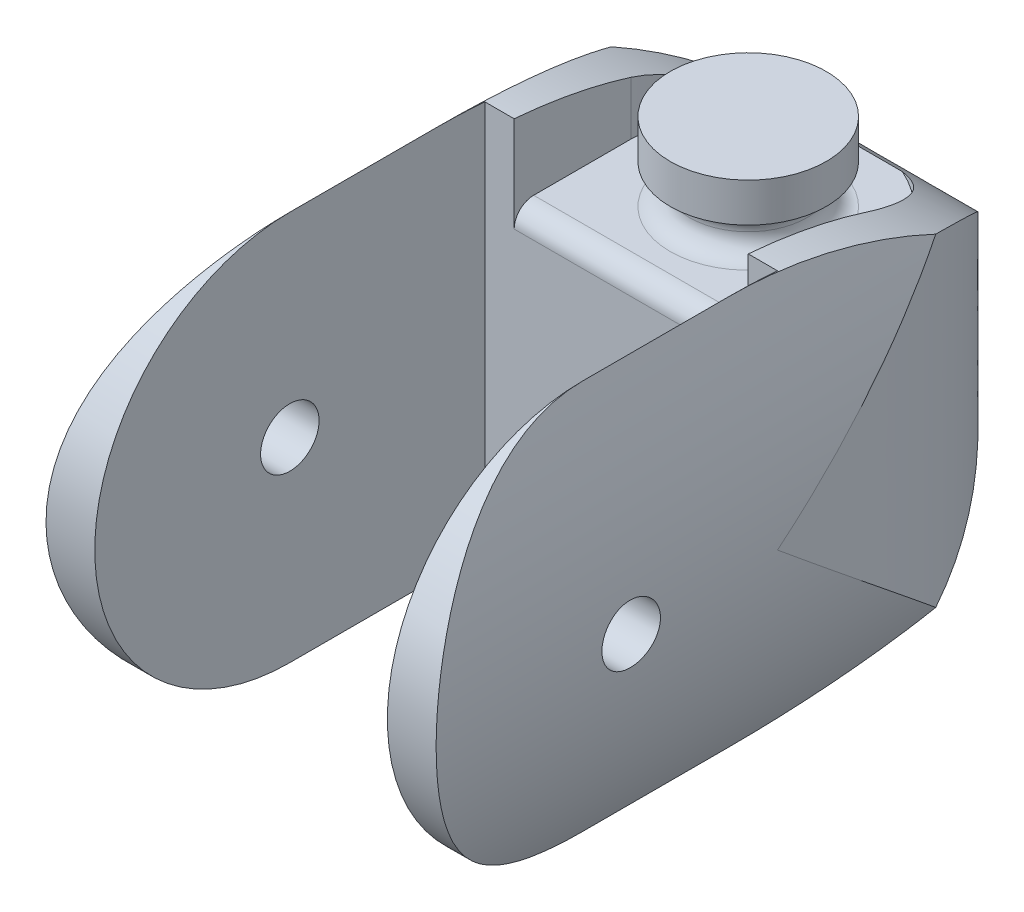
SolidWorks part; units mm, degrees
ref_plane "Alzado" through (0, 0, 0) normal (0, 0, 1) x (1, 0, 0)
ref_plane "Planta" through (0, 0, 0) normal (0, 1, 0) x (1, 0, 0)
ref_plane "Vista lateral" through (0, 0, 0) normal (1, 0, 0) x (0, 0, -1)
sketch "Croquis1" plane through (0, 0, 0) normal (0, 0, 1) x (1, 0, 0)
  line L1 (-7.5, 10) -> (7.5, 10)
  line L3 (-7.5, -10) -> (7.5, -10)
  line L5 (-7.5, 10) -> (7.5, -10) construction
  line L6 (-7.5, -10) -> (7.5, 10) construction
  arc A0 (-7.5, 10) -> (-7.5, -10) centre (11.25, 0) ccw
  arc A1 (7.5, -10) -> (7.5, 10) centre (-11.25, 0) ccw
  point P0 (0, 0)
  point P6 (-10, 0)
  point P7 (10, 0)
  dimension "D1" = 15
  dimension "D2" = 20
  dimension "D3" = 20
extrude "Saliente-Extruir1" add sketch "Croquis1" along normal blind 35
sketch "Croquis3" plane through (0, 0, 35) normal (0, 0, 1) x (1, 0, 0)
  line L0 (-7.5, -10) -> (7.5, -10) construction
  circle A0 centre (0, -7) radius 1.5
  dimension "D2" = 3
  dimension "D1" = 3
extrude "Cortar-Extruir2" cut sketch "Croquis3" against normal through all
sketch "Croquis6" plane through (0, 0, 35) normal (0, 0, 1) x (1, 0, 0)
  line L1 (-7.5, 10) -> (7.5, 10)
  line L2 (-7.5, 10) -> (-7.5, -10)
  line L3 (-7.5, -10) -> (7.5, -10)
  line L4 (7.5, 10) -> (7.5, -10)
  line L5 (-7.5, 10) -> (7.5, -10) construction
  line L6 (-7.5, -10) -> (7.5, 10) construction
  point P0 (0, 0)
extrude "Cortar-Extruir4" cut sketch "Croquis6" against normal blind 20
sketch "Croquis7" plane through (0, 0, 0) normal (1, 0, 0) x (0, 0, -1)
  line L0 (-35, 10) -> (-35, -10) construction
  line L2 (-25, -10) -> (-41, -10)
  line L4 (-25, 10) -> (-41, 10)
  line L5 (-41, -10) -> (-41, 10)
  arc A0 (-25, 10) -> (-25, -10) centre (-25, 0) ccw
  circle A1 centre (-25, 0) radius 1.5
  dimension "D2" = 3
  dimension "D1" = 10
  dimension "D3" = 16
extrude "Cortar-Extruir5" cut sketch "Croquis7" against normal through all both and the other way through all
sketch "Croquis2" plane through (0, 0, 0) normal (0, 1, 0) x (1, 0, 0)
  line L0 (10, -23.5) -> (10, 0) construction
  line L1 (7.5, 0) -> (-7.5, 0) construction
  line L9 (-1.2618, 0) -> (1.2618, 0)
  line L12 (-10, -17.5) -> (-10, 3.2701)
  line L13 (-10, 3.2701) -> (10, 3.2701)
  line L14 (10, -17.5) -> (10, 3.2701)
  ellipse E0 centre (0, -17.5) end of major axis (0, 0.141) minor radius 10 (-1.2618, 0) -> (-10, -17.5) ccw
  ellipse E1 centre (0, -17.5) end of major axis (0, 0.141) minor radius 10 (10, -17.5) -> (1.2618, 0) ccw
  dimension "D1" = 10
  dimension "D2" = 17.5
extrude "Cortar-Extruir1" cut sketch "Croquis2" against normal through all both and the other way through all
sketch "Croquis5" plane through (0, 0, 0) normal (1, 0, 0) x (0, 0, -1)
  line L0 (-15, -10) -> (-5.8316, -10) construction
  line L2 (-17.5, -10) -> (6.25, -10)
  line L4 (-17.5, 10) -> (6.25, 10)
  line L5 (6.25, -10) -> (6.25, 10)
  ellipse E0 centre (-17.5, 0) end of major axis (0, 0) minor radius 10 (-17.5, -10) -> (-17.5, 10) ccw
extrude "Cortar-Extruir3" cut sketch "Croquis5" against normal through all both and the other way through all
ref_plane "Plane1" through (0, 10, 0) normal (0, 1, 0) x (1, 0, 0)
sketch "Sketch1" plane through (0, 10, 0) normal (0, 1, 0) x (1, 0, 0)
  line L0 (10, -23.5) -> (10, -17.5) construction
  line L1 (-7.5, -15) -> (7.5, -15) construction
  line L4 (-6, -9) -> (-6, -15)
  line L5 (-6, -15) -> (6, -15)
  line L6 (6, -9) -> (6, -15)
  arc A0 (6, -9) -> (-6, -9) centre (0, -9) ccw
  dimension "D1" = 12
  dimension "D2" = 10
  dimension "D3" = 6
extrude "Cut-Extrude1" cut sketch "Sketch1" against normal blind 4
sketch "Sketch2" plane through (0, 6, 0) normal (0, 1, 0) x (1, 0, 0)
  line L0 (-6, -15) -> (6, -15) construction
  line L1 (10, -23.5) -> (10, -17.5) construction
  circle A0 centre (0, -9) radius 3
  dimension "D1" = 6
  dimension "D2" = 6
  dimension "D3" = 10
extrude "Boss-Extrude1" add sketch "Sketch2" along normal blind 2
sketch "Sketch3" plane through (0, 8, 0) normal (0, 1, 0) x (1, 0, 0)
  circle A0 centre (0, -9) radius 4
  dimension "D1" = 8
extrude "Boss-Extrude2" add sketch "Sketch3" along normal blind 2
fillet "Fillet1" radius 1 2 edges at (0, 6, 12) (0, 8, 12)
fillet "Fillet2" radius 1 1 edges at (0, 6, 15)
fillet "Fillet4" radius 1 1 edges at (1.5, -7, 15)
